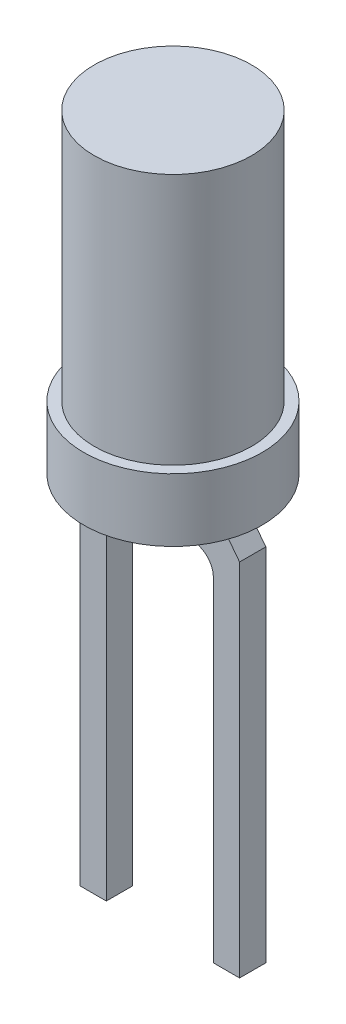
SolidWorks part; units mm, degrees
material "ABS PC"
ref_plane "Face" through (0, 0, 0) normal (0, 0, 1) x (1, 0, 0)
ref_plane "Dessus" through (0, 0, 0) normal (0, 1, 0) x (1, 0, 0)
ref_plane "Droite" through (0, 0, 0) normal (1, 0, 0) x (0, 0, -1)
sketch "Esquisse1" plane through (0, 0, 0) normal (0, 1, 0) x (1, 0, 0)
  circle A0 centre (0, 0) radius 1.5
  dimension "D1" = 3
extrude "Boss.-Extru.1" add sketch "Esquisse1" against normal blind 4.8
sketch "Esquisse2" plane through (0, -4.8, 0) normal (0, -1, 0) x (1, 0, 0)
  circle A0 centre (0, 0) radius 1.7
  dimension "D1" = 3.4
extrude "Boss.-Extru.2" add sketch "Esquisse2" along normal blind 1.2
sketch "Esquisse3" plane through (0, 0, 0) normal (0, 0, 1) x (1, 0, 0)
  line L0 (0, -6) -> (0, -13.3988) construction
  line L1 (-1.7, -6) -> (1.7, -6) construction
  line L2 (0.5, -6) -> (0.5, -6.6725)
  line L3 (0.5, -6.6725) -> (0.62, -6.6725)
  line L4 (1.02, -7.0725) -> (1.02, -13.4396)
  line L5 (-1.0841, -6) -> (-0.5, -6)
  line L6 (1.52, -13.4396) -> (1.52, -6.5725)
  line L7 (1.52, -6.5725) -> (1.0841, -6)
  line L8 (1.0841, -6) -> (0.5, -6)
  line L9 (-1.52, -6.5725) -> (-1.0841, -6)
  line L10 (-1.52, -13.4396) -> (-1.52, -6.5725)
  line L11 (-1.02, -7.0725) -> (-1.02, -13.4396)
  line L12 (-0.5, -6.6725) -> (-0.62, -6.6725)
  line L13 (-0.5, -6) -> (-0.5, -6.6725)
  line L14 (-1.52, -13.4396) -> (-1.02, -13.4396)
  line L15 (1.02, -13.4396) -> (1.52, -13.4396)
  arc A0 (0.62, -6.6725) -> (1.02, -7.0725) centre (0.62, -7.0725) cw
  arc A1 (-0.62, -6.6725) -> (-1.02, -7.0725) centre (-0.62, -7.0725) ccw
  dimension "D1" = 0.4
  dimension "D2" = 0.5
  dimension "D3" = 1.02
  dimension "D4" = 1
extrude "Boss.-Extru.3" add sketch "Esquisse3" along normal blind 0.25 and the other way blind 0.25
